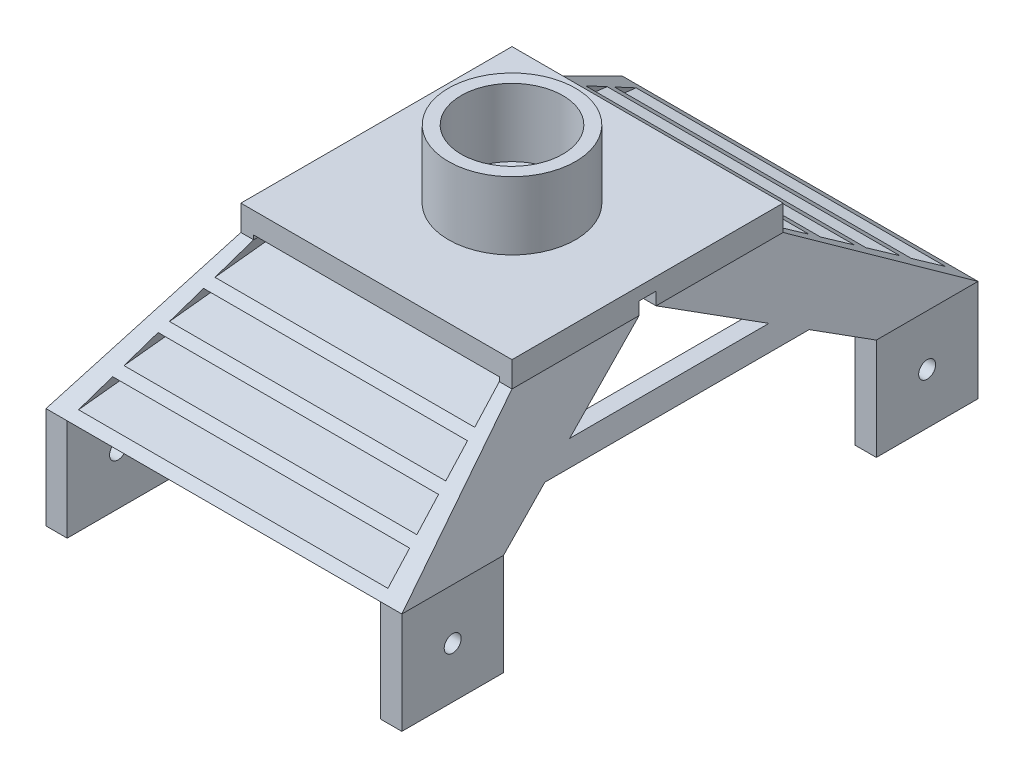
SolidWorks part; units mm, degrees
other "Markup1"
sketch "Sketch35" plane through (-42, -51, 68) normal (-0.7034, -0.6787, 0.2114) x (0.243, 0.0499, 0.9687)
material "ABS"
ref_plane "前视基准面" through (0, 0, 0) normal (0, 0, 1) x (1, 0, 0)
ref_plane "上视基准面" through (0, 0, 0) normal (0, 1, 0) x (1, 0, 0)
ref_plane "右视基准面" through (0, 0, 0) normal (1, 0, 0) x (0, 0, -1)
other "Configuration Table"
sketch "Sketch4" plane through (0, 0, 0) normal (0, 1, 0) x (1, 0, 0)
  line L0 (0, 0) -> (2.5882, 9.6593) construction
  line L1 (32, -32) -> (-32, -32)
  line L2 (32, -32) -> (32, 32)
  line L3 (32, 32) -> (-32, 32)
  line L4 (-32, -32) -> (-32, 32)
  line L5 (32, -32) -> (-32, 32) construction
  line L6 (32, 32) -> (-32, -32) construction
  line L7 (-2.5882, 9.6593) -> (-2.0706, 7.7274)
  line L8 (2.5882, 9.6593) -> (2.0706, 7.7274)
  line L9 (-32, 0) -> (32, 0) construction
  line L10 (-2.5882, -9.6593) -> (-2.0706, -7.7274)
  line L11 (2.5882, -9.6593) -> (2.0706, -7.7274)
  circle A0 centre (0, 0) radius 2.5
  arc A1 (2.5882, 9.6593) -> (-2.5882, 9.6593) centre (0, 0) ccw
  arc A2 (2.0706, 7.7274) -> (-2.0706, 7.7274) centre (0, 0) ccw
  arc A3 (2.5882, -9.6593) -> (-2.5882, -9.6593) centre (0, 0) cw
  arc A4 (2.0706, -7.7274) -> (-2.0706, -7.7274) centre (0, 0) cw
  point P0 (0, 0)
  dimension "D3" = 30
  dimension "D1" = 64
  dimension "D2" = 64
extrude "Boss-Extrude3" add sketch "Sketch4" along normal blind 3
sketch "Sketch6" plane through (0, 3, 0) normal (0, 1, 0) x (1, 0, 0)
  circle A0 centre (0, 0) radius 15
  circle A1 centre (0, 0) radius 12
extrude "Boss-Extrude4" add sketch "Sketch6" along normal blind 16
ref_plane "Plane1" through (0, -50, 0) normal (0, 1, 0) x (1, 0, 0)
sketch "Sketch8" plane through (0, -50, 0) normal (0, 1, 0) x (1, 0, 0)
  line L0 (0, -32) -> (0, 32) construction
  line L3 (-32, 0) -> (32, 0) construction
  line L7 (37, -68) -> (42, -68)
  line L8 (37, -68) -> (37, -44)
  line L9 (37, -44) -> (42, -44)
  line L10 (42, -68) -> (42, -44)
  line L18 (-37, -44) -> (-42, -44)
  line L19 (-42, -68) -> (-42, -44)
  line L20 (-37, -68) -> (-42, -68)
  line L21 (-37, -68) -> (-37, -44)
  line L22 (37, 44) -> (42, 44)
  line L23 (42, 68) -> (42, 44)
  line L24 (37, 68) -> (42, 68)
  line L25 (37, 68) -> (37, 44)
  line L26 (-37, 68) -> (-37, 44)
  line L27 (-37, 68) -> (-42, 68)
  line L28 (-42, 68) -> (-42, 44)
  line L29 (-37, 44) -> (-42, 44)
  dimension "D1" = 5
  dimension "D2" = 37
  dimension "D3" = 24
  dimension "D4" = 44
sketch "Sketch12" plane through (0, 0, 0) normal (0, -1, 0) x (1, 0, 0)
  line L0 (-32, 0) -> (32, 0) construction
  line L1 (32, 32) -> (29, 32)
  line L2 (32, 32) -> (32, 2)
  line L3 (32, 2) -> (29, 2)
  line L4 (29, 32) -> (29, 2)
  line L5 (-32, -32) -> (-32, 32) construction
  line L6 (32, 32) -> (32, -32) construction
  line L7 (0, 32) -> (0, -32) construction
  line L8 (-32, 32) -> (32, 32) construction
  line L9 (32, -32) -> (-32, -32) construction
  line L10 (32, -2) -> (29, -2)
  line L11 (29, -32) -> (29, -2)
  line L12 (32, -32) -> (29, -32)
  line L13 (32, -32) -> (32, -2)
  line L14 (-32, 2) -> (-29, 2)
  line L15 (-29, 32) -> (-29, 2)
  line L16 (-32, 32) -> (-29, 32)
  line L17 (-32, 32) -> (-32, 2)
  line L18 (-32, -32) -> (-32, -2)
  line L19 (-32, -32) -> (-29, -32)
  line L20 (-29, -32) -> (-29, -2)
  line L21 (-32, -2) -> (-29, -2)
  dimension "D1" = 3
  dimension "D2" = 30
extrude "Boss-Extrude7" add sketch "Sketch8" along normal blind 24 separate body
sketch "Sketch16" plane through (0, 0, 0) normal (1, 0, 0) x (0, 0, -1)
  line L0 (-68, -26) -> (-68, -50) construction
  line L1 (68, -26) -> (68, -50) construction
  circle A0 centre (-56, -38) radius 2
  circle A1 centre (56, -38) radius 2
  dimension "D1" = 12
  dimension "D2" = 12
extrude "Cut-Extrude3" cut sketch "Sketch16" against normal blind 85
extrude "Cut-Extrude4" cut sketch "Sketch16<2>" along normal blind 114
sketch "Sketch16<2>" plane through (0, 0, 0) normal (1, 0, 0) x (0, 0, -1) same geometry as "Sketch16"
extrude "Boss-Extrude8" add sketch "Sketch12" along normal blind 3
loft "Loft4" add section face at (-30.5, -3, -17) section face at (-39.5, -26, -56) connector at (-29, -3, -32) connector at (-37, -26, -68)
loft "Loft5" add section face at (-30.5, -3, 17) section face at (-39.5, -26, 56) connector at (-32, -3, 32) connector at (-42, -26, 68)
loft "Loft6" add section face at (30.5, -3, -17) section face at (39.5, -26, -56) connector at (32, -3, -32) connector at (42, -26, -68)
loft "Loft7" add section face at (30.5, -3, 17) section face at (39.5, -26, 56) connector at (29, -3, 32) connector at (37, -26, 68)
sketch "Sketch23" plane through (0, 0, 0) normal (0, -1, 0) x (1, 0, 0)
  line L0 (29, 32) -> (29, 2) construction
  line L1 (-29, 32) -> (29, 32)
  line L2 (-29, 32) -> (-29, 30)
  line L3 (-29, 30) -> (29, 30)
  line L4 (29, 32) -> (29, 30)
  line L5 (-32, 0) -> (32, 0) construction
  line L6 (-32, -2) -> (-32, 2) construction
  line L7 (32, 2) -> (32, -2) construction
  line L8 (-29, 2) -> (-29, 32) construction
  line L9 (-29, 22) -> (29, 22)
  line L10 (-29, 22) -> (-29, 20)
  line L11 (-29, 20) -> (29, 20)
  line L12 (29, 22) -> (29, 20)
  line L13 (-29, -10) -> (29, -10)
  line L14 (-29, 12) -> (29, 12)
  line L15 (-29, 12) -> (-29, 10)
  line L16 (-29, 10) -> (29, 10)
  line L17 (29, 12) -> (29, 10)
  line L18 (29, -12) -> (29, -10)
  line L19 (-29, -12) -> (29, -12)
  line L20 (-29, -12) -> (-29, -10)
  line L21 (-29, -20) -> (29, -20)
  line L22 (29, -22) -> (29, -20)
  line L23 (-29, -22) -> (29, -22)
  line L24 (-29, -22) -> (-29, -20)
  line L25 (-29, -30) -> (29, -30)
  line L26 (29, -32) -> (29, -30)
  line L27 (-29, -32) -> (29, -32)
  line L28 (-29, -32) -> (-29, -30)
  dimension "D1" = 2
  dimension "D2" = 2
  dimension "D3" = 8
  dimension "D4" = 2
  dimension "D5" = 8
extrude "Boss-Extrude14" add sketch "Sketch23" along normal blind 2
sketch "Sketch30" plane through (0, 0, 0) normal (1, 0, 0) x (0, 0, -1)
  line L0 (-17, -3) -> (-56, -26) construction
  line L1 (-2, -3) -> (-32, -3) construction
  line L2 (-68, -26) -> (-44, -26) construction
  line L3 (-68, -26) -> (-50.8819, -22.9816)
  line L4 (-65.8048, -24.5975) -> (-48.4257, -21.5331)
  line L5 (-32, -3) -> (-68, -26) construction
  line L6 (-41.0571, -17.1875) -> (-59.2191, -20.39)
  line L7 (-38.6009, -15.739) -> (-57.0239, -18.9875)
  line L8 (-31.2324, -11.3935) -> (-50.4382, -14.78)
  line L9 (-28.7762, -9.9449) -> (-48.243, -13.3775)
  line L10 (-21.4077, -5.5994) -> (-41.6573, -9.17)
  line L11 (-18.9515, -4.1509) -> (-39.4621, -7.7675)
  line L12 (-65.8048, -24.5975) -> (-68, -26)
  line L13 (-48.4257, -21.5331) -> (-50.8819, -22.9816)
  line L14 (-18.9515, -4.1509) -> (-21.4077, -5.5994)
  line L15 (-39.4621, -7.7675) -> (-41.6573, -9.17)
  line L16 (-48.243, -13.3775) -> (-50.4382, -14.78)
  line L17 (-57.0239, -18.9875) -> (-59.2191, -20.39)
  line L18 (-38.6009, -15.739) -> (-41.0571, -17.1875)
  line L19 (-28.7762, -9.9449) -> (-31.2324, -11.3935)
  dimension "D1" = 10
  dimension "D2" = 1
  dimension "D3" = 3
  dimension "D4" = 1
  dimension "D5" = 3
  dimension "D6" = 1
  dimension "D7" = 3
  dimension "D8" = 1
extrude "Boss-Extrude19" add sketch "Sketch30" along normal blind 45 and the other way blind 47
sketch "Sketch31" plane through (0, 0, 0) normal (0, 0, 1) x (1, 0, 0)
  line L0 (-32, -3) -> (-42, -26)
  line L1 (-42, -26) -> (-54.1068, -26)
  line L2 (-54.1068, -26) -> (-54.1068, -3)
  line L3 (-54.1068, -3) -> (-32, -3)
  line L4 (32, -3) -> (50.2676, -3)
  line L5 (50.2676, -3) -> (50.2676, -26)
  line L6 (50.2676, -26) -> (42, -26)
  line L7 (42, -26) -> (32, -3)
extrude "Cut-Extrude9" cut sketch "Sketch31" along normal blind 95
mirror "Mirror7" about plane through (0, 0, 0) normal (0, 0, 1) of "Cut-Extrude9", "Boss-Extrude19"
sketch "Sketch32" plane through (0, 0, 0) normal (0, 0, 1) x (1, 0, 0)
  line L22 (34.5609, -18.9875) -> (38.9511, -18.9875)
  line L23 (-34.5609, -18.9875) -> (34.5609, -18.9875) construction
  line L24 (33.0974, -14.78) -> (34.5609, -18.9875) construction
  line L25 (32, -3) -> (42, -26) construction
  line L26 (34.5609, -18.9875) -> (33.0974, -14.78)
  line L27 (33.0974, -14.78) -> (37.1217, -14.78)
  line L28 (37.1217, -14.78) -> (38.9511, -18.9875)
extrude "Boss-Extrude21" add sketch "Sketch32" along normal blind 44 and the other way blind 37
mirror "Mirror8" about plane through (0, 0, 0) normal (1, 0, 0) of "Boss-Extrude21"
ref_plane "Plane2" through (0, -15, 0) normal (0, 1, 0) x (1, 0, 0)
sketch "Sketch34" plane through (0, -15, 0) normal (0, 1, 0) x (1, 0, 0)
  line L0 (-32, 0) -> (49968, 0) construction
  line L3 (-32, 2) -> (-32, -2) construction
  line L8 (32, -2) -> (32, 2) construction
  line L10 (-9, -10) -> (-5, -10)
  line L11 (-9, -10) -> (-9, 10)
  line L12 (-9, 10) -> (-5, 10)
  line L13 (-5, -10) -> (-5, 10)
  line L14 (-9, -10) -> (-5, 10) construction
  line L15 (-9, 10) -> (-5, -10) construction
  point P4 (-32, 0)
  point P7 (32, 0)
  point P8 (-7, 0)
  point P14 (-5, 0)
  dimension "D1" = 5
  dimension "D2" = 4
  dimension "D3" = 20
extrude "Boss-Extrude23" add sketch "Sketch34" against normal blind 25
extrude "Boss-Extrude24" add sketch "Sketch34<2>" along normal blind 17 and the other way blind 35
sketch "Sketch34<2>" plane through (0, -15, 0) normal (0, 1, 0) x (1, 0, 0) same geometry as "Sketch34"
